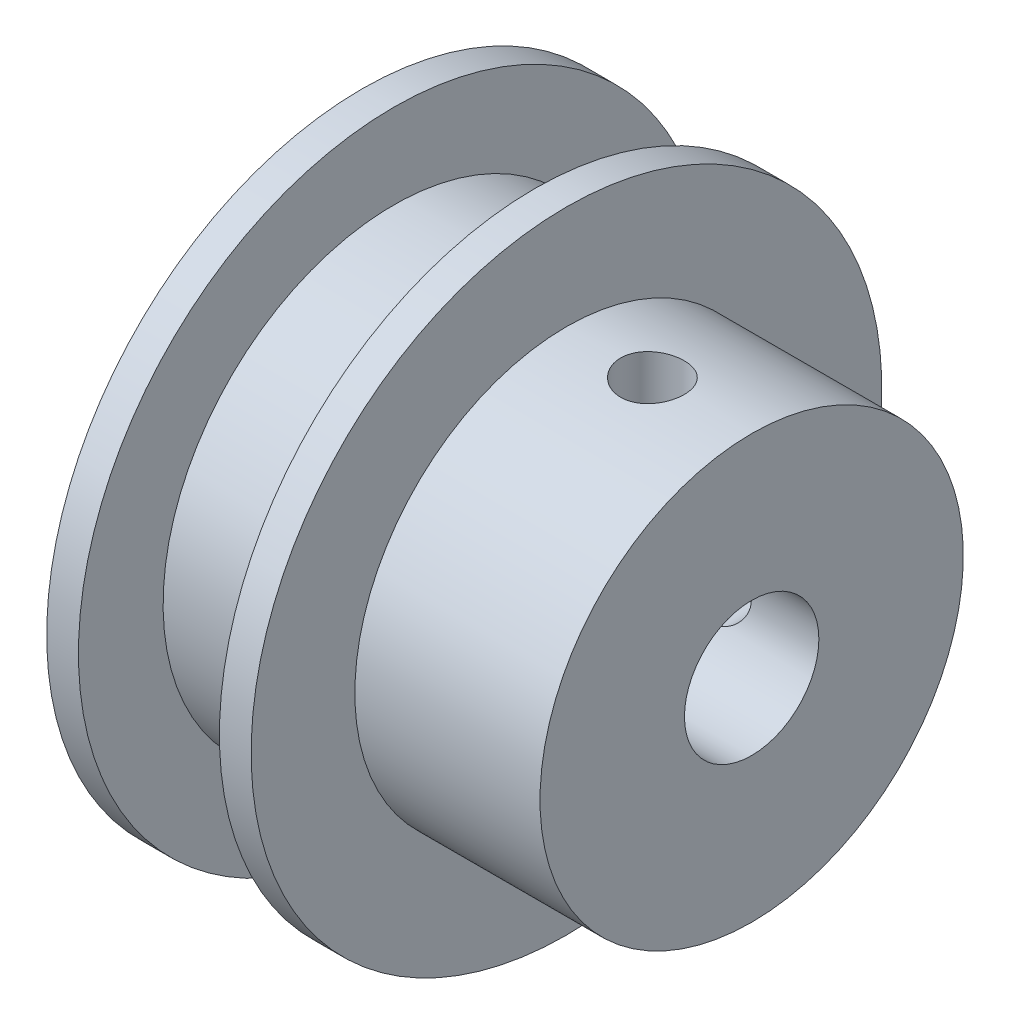
SolidWorks part; units mm, degrees
ref_plane "Front Plane" through (0, 0, 0) normal (0, 0, 1) x (1, 0, 0)
ref_plane "Top Plane" through (0, 0, 0) normal (0, 1, 0) x (1, 0, 0)
ref_plane "Right Plane" through (0, 0, 0) normal (1, 0, 0) x (0, 0, -1)
sketch "Sketch1" plane through (0, 0, 0) normal (0, 0, 1) x (1, 0, 0)
  line L0 (-3.33, 0) -> (3.33, 0)
  line L1 (-3.33, 0) -> (-3.33, 4)
  line L2 (-3.33, 4) -> (-4.83, 4)
  line L3 (-4.83, 4) -> (-4.83, -10.9)
  line L4 (-4.83, -10.9) -> (13.58, -10.9)
  line L5 (13.58, -10.9) -> (13.58, -0.9)
  line L6 (13.58, -0.9) -> (4.83, -0.9)
  line L7 (4.83, -0.9) -> (4.83, 4)
  line L8 (4.83, 4) -> (3.33, 4)
  line L9 (3.33, 4) -> (3.33, 0)
  point P4 (0, 0)
  dimension "D1" = 14.9
  dimension "D2" = 1.5
  dimension "D3" = 10
  dimension "D4" = 4
  dimension "D5" = 6.66
  dimension "D6" = 8.75
revolve "Revolve1" add sketch "Sketch1" angle 360 about L4
sketch "Sketch4" plane through (13.58, 0, 0) normal (1, 0, 0) x (0, 0, -1)
  line L0 (0, -0.9) -> (0, -10.9) construction
  circle A0 centre (0, -10.9) radius 10 construction
  circle A1 centre (0, -10.9) radius 3.175
  dimension "D1" = 6.35
extrude "Cut-Extrude1" cut sketch "Sketch4" against normal through all both and the other way through all
sketch "Sketch5" plane through (0, 0, 0) normal (0, 0, 1) x (1, 0, 0)
  line L0 (0, 0) -> (0, -10.9) construction
  line L1 (0, -10.9) -> (8.89, -10.9) construction
  circle A0 centre (8.89, -10.9) radius 1.5
  point P0 (9.3352, -10.9)
  point P6 (10.169, -11.9904)
  dimension "D2" = 3
  dimension "D1" = 10.9
  dimension "D3" = 8.89
extrude "Cut-Extrude2" cut sketch "Sketch5" against normal up to surface (10 mm away) up to face at (4.83, -20.9, 0)
sketch "Sketch8" plane through (0, 0, 0) normal (0, 1, 0) x (1, 0, 0)
  line L0 (0, 0) -> (8.89, 0) construction
  circle A0 centre (8.89, 0) radius 1.5
  dimension "D2" = 3
  dimension "D1" = 8.89
extrude "Cut-Extrude3" cut sketch "Sketch8" against normal up to surface (8.1017 mm away) up to face at (7.3997, -10.7293, -3.1704)
